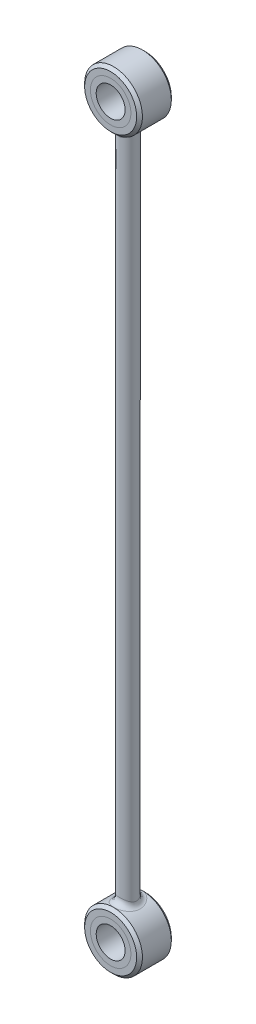
SolidWorks part; units mm, degrees
ref_plane "Front Plane" through (0, 0, 0) normal (0, 0, 1) x (1, 0, 0)
ref_plane "Top Plane" through (0, 0, 0) normal (0, 1, 0) x (1, 0, 0)
ref_plane "Right Plane" through (0, 0, 0) normal (1, 0, 0) x (0, 0, -1)
sketch "Sketch1" plane through (0, 0, 0) normal (0, 1, 0) x (1, 0, 0)
  circle A0 centre (0, 0) radius 1.5
  dimension "D1" = 3
extrude "Boss-Extrude1" add sketch "Sketch1" along normal mid plane 117
sketch "Sketch2" plane through (0, 0, 0) normal (0, 0, 1) x (1, 0, 0)
  circle A0 centre (0, 63) radius 5
  circle A1 centre (0, -63) radius 5
  circle A2 centre (0, 63) radius 3.5
  circle A3 centre (0, -63) radius 3.5
  dimension "D1" = 10
  dimension "D2" = 63
  dimension "D3" = 10
  dimension "D5" = 7
  dimension "D6" = 7
  dimension "D4" = 63
extrude "Boss-Extrude2" add sketch "Sketch2" along normal mid plane 6
sketch "Sketch3" plane through (0, 0, 0) normal (0, 0, 1) x (1, 0, 0)
  circle A0 centre (0, 63) radius 3.5
  circle A1 centre (0, 63) radius 2.5
  circle A2 centre (0, -63) radius 3.5
  circle A3 centre (0, -63) radius 2.5
  dimension "D1" = 7
  dimension "D2" = 5
  dimension "D3" = 7
  dimension "D4" = 5
extrude "Boss-Extrude3" add sketch "Sketch3" along normal mid plane 6 separate body
fillet "Fillet1" radius 1 2 edges at (-0.2714, -58.0074, 1.4752) (0.2714, 58.0074, 1.4752)
chamfer "Chamfer2" distance 0.5 angle 45 4 edges at (5, -63, 3) (5, -63, -3) (5, 63, -3) (5, 63, 3)
